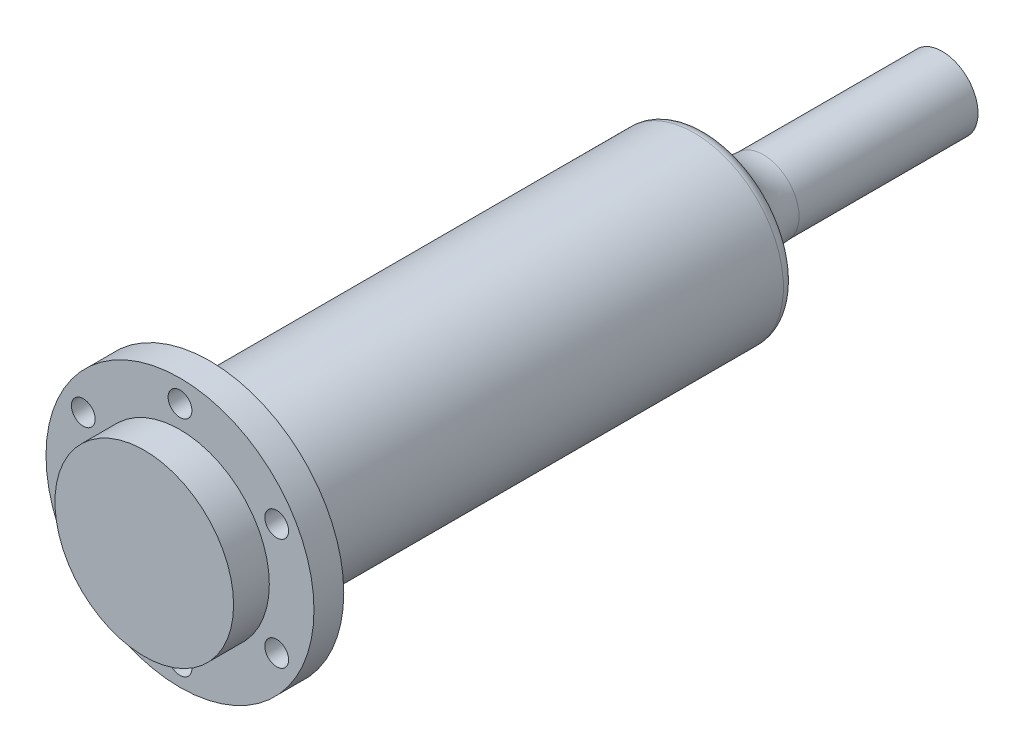
SolidWorks part; units mm, degrees
material "6063-O, Extruded Rod (SS)"
ref_plane "Front Plane" through (0, 0, 0) normal (0, 0, 1) x (1, 0, 0)
ref_plane "Top Plane" through (0, 0, 0) normal (0, 1, 0) x (1, 0, 0)
ref_plane "Right Plane" through (0, 0, 0) normal (1, 0, 0) x (0, 0, -1)
sketch "Sketch1" plane through (0, 0, 0) normal (0, 0, 1) x (1, 0, 0)
  circle A0 centre (0, 0) radius 15
  dimension "D1" = 30
extrude "Boss-Extrude1" add sketch "Sketch1" along normal blind 77
sketch "Sketch3" plane through (0, 0, 77) normal (0, 0, 1) x (1, 0, 0)
  circle A0 centre (0, 0) radius 7.5
  circle A1 centre (0, 0) radius 15
  dimension "D1" = 30
  dimension "D2" = 15
extrude "Boss-Extrude2" add sketch "Sketch3" along normal blind 17
sketch "Sketch4" plane through (0, 0, 94) normal (0, 0, 1) x (1, 0, 0)
  circle A0 centre (0, 0) radius 12.5
  circle A1 centre (0, 0) radius 22.5
  circle A2 centre (0, 0) radius 18.75 construction
  circle A3 centre (0, 18.75) radius 2
  circle A7 centre (16.238, 9.375) radius 2
  circle A8 centre (16.238, -9.375) radius 2
  circle A9 centre (0, -18.75) radius 2
  circle A10 centre (-16.238, -9.375) radius 2
  circle A11 centre (-16.238, 9.375) radius 2
  point P16 (0, 0)
  point P20 (0, 0)
  dimension "D1" = 25
  dimension "D2" = 45
  dimension "D3" = 37.5
  dimension "D4" = 4
  dimension "D5" = 6
extrude "Boss-Extrude3" add sketch "Sketch4" against normal blind 5 from offset 6 offset against normal yes
sketch "Sketch6" plane through (0, 0, 0) normal (0, 0, -1) x (-1, 0, 0)
  circle A0 centre (0, 0) radius 6
  circle A1 centre (0, 0) radius 3
  dimension "D1" = 6
  dimension "D2" = 12
extrude "Boss-Extrude4" add sketch "Sketch6" along normal blind 40
sketch "Sketch7" plane through (0, 0, -40) normal (0, 0, -1) x (-1, 0, 0)
  line L0 (0, 0) -> (0, 6) construction
  circle A0 centre (0, 0) radius 6 construction
  circle A1 centre (0, 0) radius 6 construction
ref_plane "Plane1" through (0, 6, -40) normal (0, 1, 0) x (1, 0, 0)
sketch "Sketch9" plane through (0, 0, 77) normal (0, 0, 1) x (1, 0, 0)
  circle A0 centre (0, 0) radius 7.5
  dimension "D1" = 15
extrude "Cut-Extrude2" cut sketch "Sketch9" against normal offset from surface (72 mm away) 5 up to face at (-3, 0, 0)
sketch "Sketch10" plane through (0, 0, 0) normal (0, 0, -1) x (-1, 0, 0)
  circle A0 centre (0, 0) radius 3
  dimension "D1" = 6
sketch "Sketch12" plane through (0, 0, 94) normal (0, 0, 1) x (1, 0, 0)
  circle A0 centre (0, 0) radius 7.5
extrude "Cut-Extrude3" cut sketch "Sketch10" against normal up to surface (5 mm away) up to face at (7.5, 0, 5)
sketch "Sketch11" plane through (0, 0, 94) normal (0, 0, 1) x (1, 0, 0)
  circle A0 centre (0, 0) radius 7.5
fillet "Fillet1" radius 10 1 edges at (6, 0, 0)
fillet "Fillet2" radius 2 1 edges at (15, 0, 0)
extrude "Boss-Extrude5" add sketch "Sketch12" against normal up to surface (89 mm away) contours A0 up to face at (3, 0, 5)
other "DeleteFace2" face at (-3, 0, -40) face at (3, 0, 5) and patch yes
